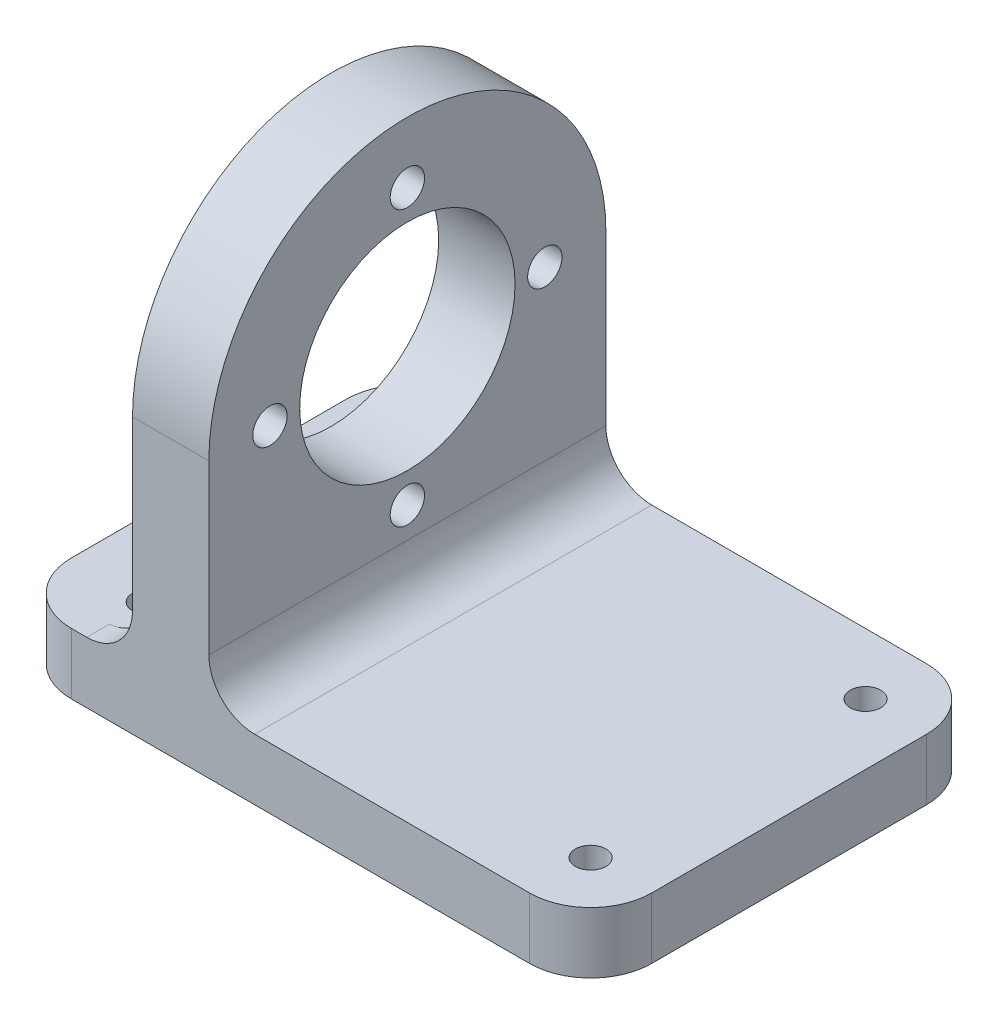
SolidWorks part; units mm, degrees
ref_plane "Front Plane" through (0, 0, 0) normal (0, 0, 1) x (1, 0, 0)
ref_plane "Top Plane" through (0, 0, 0) normal (0, 1, 0) x (1, 0, 0)
ref_plane "Right Plane" through (0, 0, 0) normal (1, 0, 0) x (0, 0, -1)
sketch "Sketch1" plane through (0, 0, 0) normal (1, 0, 0) x (0, 0, -1)
  line L0 (-13, 0) -> (-13, -18)
  line L1 (13, 0) -> (13, -18)
  line L2 (-13, -18) -> (13, -18)
  circle A0 centre (0, 0) radius 9 construction
  circle A1 centre (0, 9) radius 1.125
  circle A2 centre (9, 0) radius 1.125
  circle A3 centre (0, -9) radius 1.125
  circle A4 centre (-9, 0) radius 1.125
  arc A5 (-13, 0) -> (13, 0) centre (0, 0) cw
  circle A6 centre (0, 0) radius 7.05
  dimension "D1" = 18
  dimension "D2" = 2.25
  dimension "D3" = 13
  dimension "D5" = 14.1
  dimension "D4" = 18
extrude "Boss-Extrude1" add sketch "Sketch1" along normal blind 5
sketch "Sketch2" plane through (0, 0, 0) normal (-1, 0, 0) x (0, 0, 1)
  line L0 (13, 0) -> (13, -18) construction
  line L1 (-13, -18) -> (13, -18)
  line L2 (-13, -18) -> (-13, -14)
  line L3 (-13, -14) -> (13, -14)
  line L4 (13, -18) -> (13, -14)
  dimension "D1" = 4
extrude "Boss-Extrude2" add sketch "Sketch2" along normal blind 8 and the other way blind 30
fillet "Fillet1" radius 3 2 edges at (5, -14, 0) (0, -14, 0)
fillet "Fillet2" radius 4 4 edges at (30, -16, -13) (30, -16, 13) (-8, -16, -13) (-8, -16, 13)
sketch "Sketch3" plane through (0, -14, 0) normal (0, 1, 0) x (1, 0, 0)
  line L0 (-3, -13) -> (-3, 13) construction
  line L1 (30, -9) -> (30, 9) construction
  circle A0 centre (-3, -9) radius 1
  circle A1 centre (-3, 9) radius 1
  circle A2 centre (26, 9) radius 1
  circle A3 centre (26, -9) radius 1
  dimension "D1" = 2
  dimension "D2" = 4
  dimension "D3" = 4
  dimension "D4" = 4
extrude "Cut-Extrude1" cut sketch "Sketch3" along normal through all both and the other way through all
sketch "Sketch4" plane through (0, -14, 0) normal (0, 1, 0) x (1, 0, 0)
  circle A0 centre (-3, 9) radius 2.5
  circle A1 centre (-3, -9) radius 2.5
  dimension "D1" = 5
extrude "Cut-Extrude3" cut sketch "Sketch4" along normal up to next
